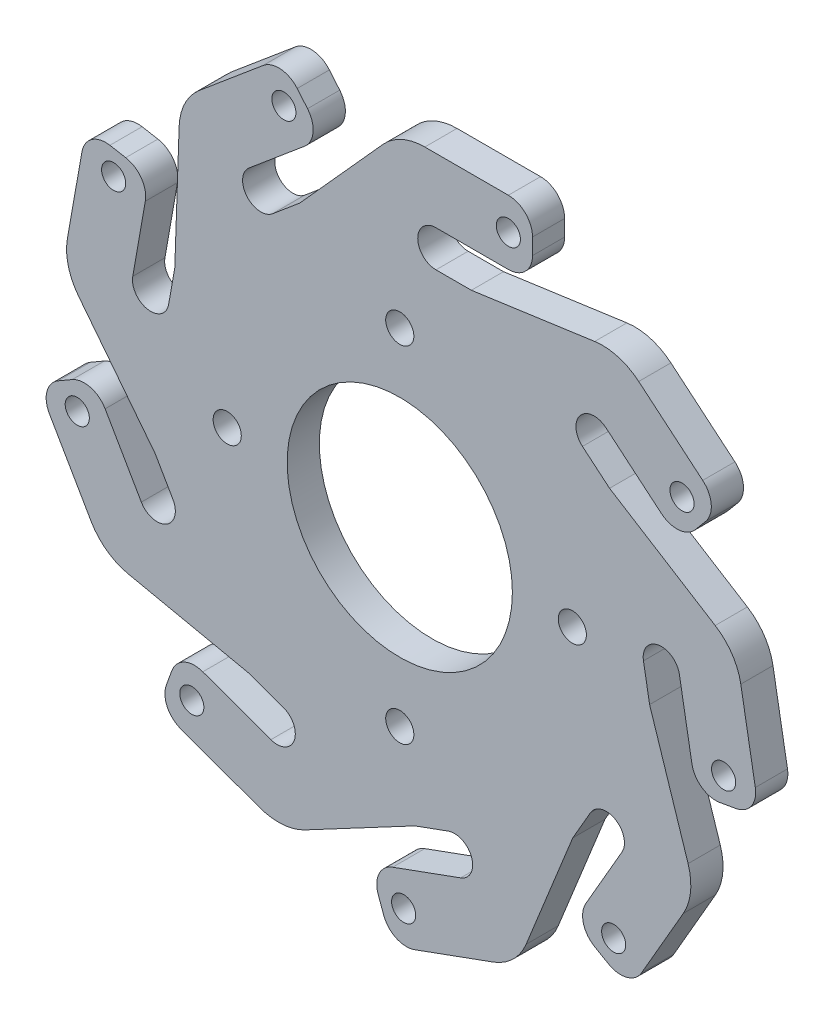
SolidWorks part; units mm, degrees
ref_plane "Front Plane" through (0, 0, 0) normal (0, 0, 1) x (1, 0, 0)
ref_plane "Top Plane" through (0, 0, 0) normal (0, 1, 0) x (1, 0, 0)
ref_plane "Right Plane" through (0, 0, 0) normal (1, 0, 0) x (0, 0, -1)
sketch "Sketch1" plane through (0, 0, 0) normal (0, 0, 1) x (1, 0, 0)
  line L0 (0, 45) -> (0, 0) construction
  line L1 (0, 0) -> (-31.8198, 31.8198) construction
  line L2 (-12.4458, 28.6775) -> (-2.0854, 40.1839)
  line L3 (3.1166, 42.5) -> (13.5, 42.5)
  line L4 (16.5, 39.5) -> (16.5, 37.5)
  line L5 (13.5, 34.5) -> (4.5, 34.5)
  line L6 (4.5, 29.9683) -> (8.8995, 29.9683)
  line L8 (29.7059, 30.5536) -> (37.6601, 23.8793)
  line L9 (38.0298, 19.6528) -> (36.7443, 18.1207)
  line L10 (32.5178, 17.7509) -> (25.6234, 23.536)
  line L11 (22.7104, 20.0645) -> (26.0807, 17.2365)
  line L12 (26.0807, 17.2365) -> (39.2113, 9.0316)
  line L13 (42.3955, 4.3108) -> (44.1986, -5.9149)
  line L14 (41.7651, -9.3902) -> (39.7955, -9.7375)
  line L15 (36.3201, -7.304) -> (34.7573, 1.5592)
  line L16 (30.2944, 0.7723) -> (31.0584, -3.5604)
  line L17 (31.0584, -3.5604) -> (35.843, -18.2859)
  line L18 (35.2478, -23.9491) -> (30.0561, -32.9413)
  line L19 (25.958, -34.0394) -> (24.226, -33.0394)
  line L20 (23.1279, -28.9413) -> (27.6279, -21.1471)
  line L21 (23.7033, -18.8813) -> (21.5035, -22.6913)
  line L22 (21.5035, -22.6913) -> (15.7034, -37.0473)
  line L23 (11.6072, -41.0029) -> (1.85, -44.5542)
  line L24 (-1.9951, -42.7612) -> (-2.6792, -40.8818)
  line L25 (-0.8862, -37.0367) -> (7.5711, -33.9585)
  line L26 (6.0211, -29.7001) -> (1.8869, -31.2048)
  line L27 (1.8869, -31.2048) -> (-11.7841, -38.4738)
  line L28 (-17.4645, -38.871) -> (-27.2217, -35.3197)
  line L29 (-29.0147, -31.4745) -> (-28.3307, -29.5951)
  line L30 (-24.4855, -27.8021) -> (-16.0283, -30.8803)
  line L31 (-14.4784, -26.6219) -> (-18.6126, -25.1172)
  line L32 (-18.6126, -25.1172) -> (-33.7576, -21.898)
  line L33 (-38.3644, -18.5509) -> (-43.5561, -9.5587)
  line L34 (-42.458, -5.4606) -> (-40.726, -4.4606)
  line L35 (-36.6279, -5.5587) -> (-32.1279, -13.3529)
  line L36 (-28.2033, -11.087) -> (-30.403, -7.2769)
  line L37 (-30.403, -7.2769) -> (-39.9356, 4.9241)
  line L38 (-41.3131, 10.4493) -> (-39.5101, 20.675)
  line L39 (-36.0347, 23.1084) -> (-34.0651, 22.7611)
  line L40 (-31.6316, 19.2858) -> (-33.1945, 10.4225)
  line L41 (-28.7316, 9.6356) -> (-27.9676, 13.9682)
  line L42 (-27.9676, 13.9682) -> (-27.4272, 29.4422)
  line L43 (-24.931, 34.5602) -> (-16.9769, 41.2345)
  line L44 (-12.7504, 40.8648) -> (-11.4648, 39.3327)
  line L45 (-11.8346, 35.1062) -> (-18.729, 29.3211)
  line L46 (-15.816, 25.8496) -> (-12.4458, 28.6775)
  line L47 (8.8995, 29.9683) -> (24.2322, 32.1231)
  line L48 (-2.4819, 28.3687) -> (0, 28.7175)
  circle A0 centre (0, 0) radius 45 construction
  circle A1 centre (0, 0) radius 14
  circle A2 centre (0, 0) radius 21.45 construction
  circle A3 centre (0, 21.45) radius 1.75
  circle A4 centre (21.45, 0) radius 1.75
  circle A5 centre (0, -21.45) radius 1.75
  circle A6 centre (-21.45, 0) radius 1.75
  arc A7 (-2.0854, 40.1839) -> (3.1166, 42.5) centre (3.1166, 35.5) cw
  arc A8 (13.5, 42.5) -> (16.5, 39.5) centre (13.5, 39.5) cw
  arc A9 (13.5, 34.5) -> (16.5, 37.5) centre (13.5, 37.5) ccw
  arc A10 (4.5, 34.5) -> (4.5, 29.9683) centre (4.5, 32.2341) ccw
  arc A11 (24.2322, 32.1231) -> (29.7059, 30.5536) centre (25.2064, 25.1913) cw
  arc A12 (37.6601, 23.8793) -> (38.0298, 19.6528) centre (35.7317, 21.5811) cw
  arc A13 (32.5178, 17.7509) -> (36.7443, 18.1207) centre (34.4461, 20.049) ccw
  arc A14 (25.6234, 23.536) -> (22.7104, 20.0645) centre (24.1669, 21.8002) ccw
  arc A15 (39.2113, 9.0316) -> (42.3955, 4.3108) centre (35.5019, 3.0953) cw
  arc A16 (44.1986, -5.9149) -> (41.7651, -9.3902) centre (41.2442, -6.4358) cw
  arc A17 (36.3201, -7.304) -> (39.7955, -9.7375) centre (39.2745, -6.7831) ccw
  arc A18 (34.7573, 1.5592) -> (30.2944, 0.7723) centre (32.5258, 1.1658) ccw
  arc A19 (35.843, -18.2859) -> (35.2478, -23.9491) centre (29.1856, -20.4491) cw
  arc A20 (30.0561, -32.9413) -> (25.958, -34.0394) centre (27.458, -31.4413) cw
  arc A21 (23.1279, -28.9413) -> (24.226, -33.0394) centre (25.726, -30.4413) ccw
  arc A22 (27.6279, -21.1471) -> (23.7033, -18.8813) centre (25.6656, -20.0142) ccw
  arc A23 (15.7034, -37.0473) -> (11.6072, -41.0029) centre (9.2131, -34.425) cw
  arc A24 (1.85, -44.5542) -> (-1.9951, -42.7612) centre (0.8239, -41.7351) cw
  arc A25 (-0.8862, -37.0367) -> (-2.6792, -40.8818) centre (0.1399, -39.8557) ccw
  arc A26 (7.5711, -33.9585) -> (6.0211, -29.7001) centre (6.7961, -31.8293) ccw
  arc A27 (-11.7841, -38.4738) -> (-17.4645, -38.871) centre (-15.0704, -32.2931) cw
  arc A28 (-27.2217, -35.3197) -> (-29.0147, -31.4745) centre (-26.1956, -32.5006) cw
  arc A29 (-24.4855, -27.8021) -> (-28.3307, -29.5951) centre (-25.5116, -30.6212) ccw
  arc A30 (-16.0283, -30.8803) -> (-14.4784, -26.6219) centre (-15.2533, -28.7511) ccw
  arc A31 (-33.7576, -21.898) -> (-38.3644, -18.5509) centre (-32.3022, -15.0509) cw
  arc A32 (-43.5561, -9.5587) -> (-42.458, -5.4606) centre (-40.958, -8.0587) cw
  arc A33 (-36.6279, -5.5587) -> (-40.726, -4.4606) centre (-39.226, -7.0587) ccw
  arc A34 (-32.1279, -13.3529) -> (-28.2033, -11.087) centre (-30.1656, -12.22) ccw
  arc A35 (-39.9356, 4.9241) -> (-41.3131, 10.4493) centre (-34.4195, 9.2338) cw
  arc A36 (-39.5101, 20.675) -> (-36.0347, 23.1084) centre (-36.5557, 20.154) cw
  arc A37 (-31.6316, 19.2858) -> (-34.0651, 22.7611) centre (-34.586, 19.8067) ccw
  arc A38 (-33.1945, 10.4225) -> (-28.7316, 9.6356) centre (-30.963, 10.029) ccw
  arc A39 (-27.4272, 29.4422) -> (-24.931, 34.5602) centre (-20.4315, 29.1979) cw
  arc A40 (-16.9769, 41.2345) -> (-12.7504, 40.8648) centre (-15.0485, 38.9364) cw
  arc A41 (-11.8346, 35.1062) -> (-11.4648, 39.3327) centre (-13.7629, 37.4043) ccw
  arc A42 (-18.729, 29.3211) -> (-15.816, 25.8496) centre (-17.2725, 27.5853) ccw
  circle A43 centre (13.5, 38.5) radius 1.5
  circle A44 centre (35.0889, 20.8151) radius 1.5
  circle A45 centre (40.2593, -6.6094) radius 1.5
  circle A46 centre (26.592, -30.9413) radius 1.5
  circle A47 centre (0.4819, -40.7954) radius 1.5
  circle A48 centre (-25.8536, -31.5609) radius 1.5
  circle A49 centre (-40.092, -7.5587) radius 1.5
  circle A50 centre (-35.5708, 19.9804) radius 1.5
  circle A51 centre (-14.4057, 38.1703) radius 1.5
  point P16 (0, 0)
  point P22 (0, 42.5)
  point P33 (16.5, 38.5)
  point P146 (0, 0)
  point P159 (0, 0)
  dimension "D1" = 90
  dimension "D2" = 28
  dimension "D3" = 42.9
  dimension "D4" = 3.5
  dimension "D7" = 7
  dimension "D9" = 3
  dimension "D15" = 3
  dimension "D6" = 45
  dimension "D8" = 132
  dimension "D10" = 8
  dimension "D11" = 13.5
  dimension "D12" = 9
  dimension "D13" = 42.5
  dimension "D16" = 9
  dimension "D5" = 4
  dimension "D14" = 9
base flange "Base-Flange1" sketch "Sketch1" thickness 4 reverse thickness direction no parameters "D1"=0.7366
sketch "Sketch6" plane through (0, 0, 0) normal (0, 0, 1) x (1, 0, 0)
  line L0 (7, 42.5) -> (7, 34.5)
  line L1 (13.5, 42.5) -> (3.1166, 42.5) construction
  line L2 (4.5, 34.5) -> (13.5, 34.5) construction
  line L3 (32.6808, 28.0574) -> (27.5385, 21.929)
  line L4 (43.0699, 0.4864) -> (35.1914, -0.9028)
  line L5 (33.3061, -27.3122) -> (26.3779, -23.3122)
  line L6 (7.958, -42.3311) -> (5.2218, -34.8135)
  line L7 (-21.1137, -37.5428) -> (-18.3775, -30.0253)
  line L8 (-40.3061, -15.1878) -> (-33.3779, -11.1878)
  line L9 (-40.6388, 14.2737) -> (-32.7603, 12.8845)
  line L10 (-21.9562, 37.0564) -> (-16.8139, 30.928)
  arc A0 (4.5, 34.5) -> (4.5, 29.9683) centre (4.5, 32.2341) ccw construction
  point P28 (0, 0)
  dimension "D1" = 2.5
  dimension "D2" = 9
sketch "Bend-Lines1" [suppressed] plane through (0, 0, 0) normal (0, 1, 0) x (1, 0, 0)
sketch "Bounding-Box1" [suppressed] plane through (0, 0, 0) normal (0, 1, 0) x (1, 0, 0)
sheet metal parameters "Sheet-Metal1" thickness 4 parameters "D1"=0.7366
flat pattern "Flat-Pattern1" [suppressed]
sketch "Bend-Lines2" plane through (0, 0, 0) normal (0, 0, 1) x (1, 0, 0)
sketch3d "Bounding-Box2" [suppressed]
  line L0 (-56.2751, -83.5937, 0) -> (31.8948, -80.8486, 0) construction
  line L1 (-58.9863, 3.4902, 0) -> (29.1835, 6.2352, 0) construction
  line L2 (-56.2751, -83.5937, 0) -> (-58.9863, 3.4902, 0) construction
  line L3 (31.8948, -80.8486, 0) -> (29.1835, 6.2352, 0) construction
